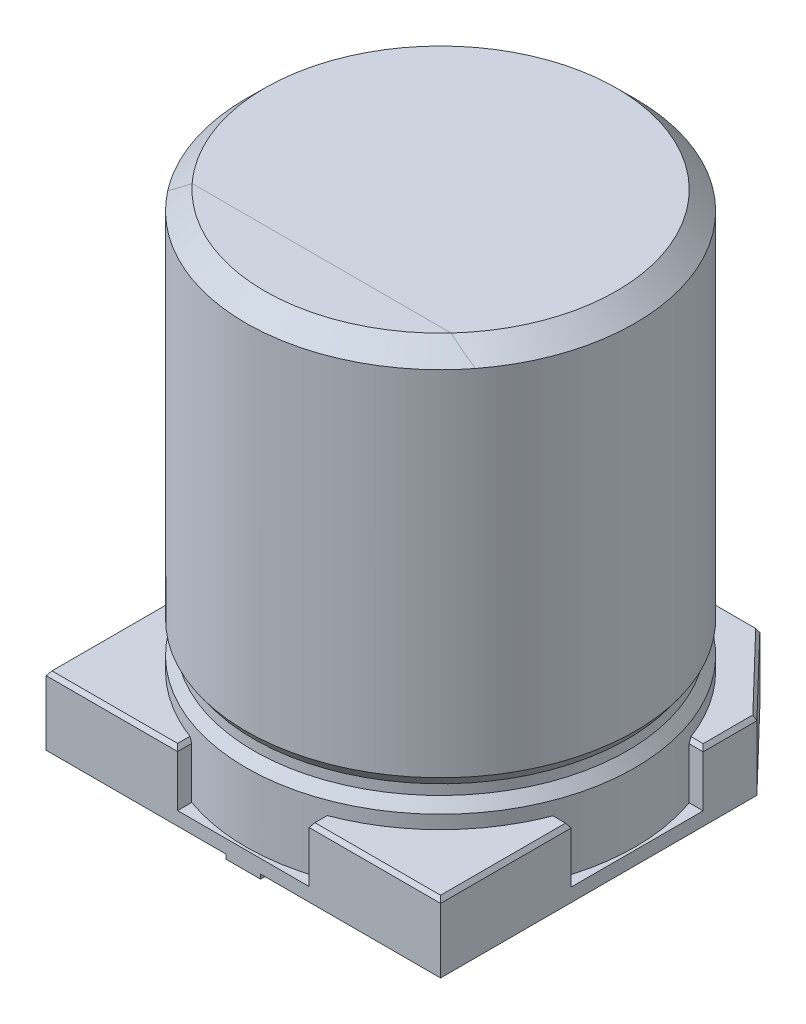
SolidWorks part; units mm, degrees
ref_plane "Front Plane" through (0, 0, 0) normal (0, 0, 1) x (1, 0, 0)
ref_plane "Top Plane" through (0, 0, 0) normal (0, 1, 0) x (1, 0, 0)
ref_plane "Right Plane" through (0, 0, 0) normal (1, 0, 0) x (0, 0, -1)
sketch "Sketch1" plane through (0, 0, 0) normal (0, 1, 0) x (1, 0, 0)
  line L0 (0, 3.315) -> (0, -3.315) construction
  point P2 (0, 0)
  line B0 (3.315, -3.315) -> (3.315, 2.0024)
  line B1 (0.2896, -3.315) -> (3.315, -3.315)
  line B2 (2.0517, 3.315) -> (3.315, 2.0024)
  line B3 (2.0517, 3.315) -> (0.2875, 3.315)
  line B4 (0.2882, 1.5924) -> (0.2875, 3.315)
  line B5 (0.2875, 3.315) -> (-0.2875, 3.315)
  line B6 (-0.2875, 3.315) -> (-0.2882, 1.5924)
  line B7 (-0.2875, 3.315) -> (-2.0519, 3.315)
  line B8 (-0.2882, 1.5924) -> (0.2882, 1.5924)
  line B9 (0.2889, -1.5924) -> (-0.2889, -1.5924)
  line B10 (0.2896, -3.315) -> (0.2889, -1.5924)
  line B11 (-0.2889, -1.5924) -> (-0.2896, -3.315)
  line B12 (-0.2896, -3.315) -> (0.2896, -3.315)
  line B13 (-3.315, -3.315) -> (-0.2896, -3.315)
  line B14 (-3.315, 2.0024) -> (-3.315, -3.315)
  line B15 (-3.315, 2.0024) -> (-2.0519, 3.315)
  line B16 (-3.315, -1.1187) -> (-1.11, -1.105)
  line B17 (-1.11, -1.105) -> (-1.105, -3.315)
  line B18 (-1.115, 1.105) -> (-3.315, 1.0983)
  line B19 (-1.12, 3.315) -> (-1.115, 1.105)
  line B20 (1.11, -1.105) -> (3.315, -1.1187)
  line B21 (1.105, -3.315) -> (1.11, -1.105)
  line B22 (1.115, 1.105) -> (1.12, 3.315)
  line B23 (3.315, 1.0983) -> (1.115, 1.105)
sketch_block_instance "Block1-1"
sketch_block "Block1"
extrude "Boss-Extrude1" add sketch "Sketch1" against normal blind 0.1571 contours B19 B7 B15 B14 B18 | L0 B8 B6 B7 B19 B18 B14 B16 B17 B13 B11 B9 | B17 B16 B14 B13 | B9 L0 B12 B10 | L0 B9 B11 B12 | L0 B5 B6 B8 | B5 L0 B8 B4 | B8 L0 B9 B10 B1 B21 B20 B0 B23 B22 B3 B4 | B23 B0 B2 B3 B22 | B21 B1 B0 B20 region at (0.1439, 0, -2.4533) region at (-0.1439, 0, -2.4533) region at (1.3107, 0, -0.0031) region at (-1.3107, 0, -0.0031) region at (0.1446, 0, 2.454) region at (-0.1446, 0, 2.454) region at (2.0777, 0, -2.0703) region at (-2.0777, 0, -2.0704) region at (-2.2101, 0, 2.2138) region at (2.2101, 0, 2.2138)
extrude "Boss-Extrude2" add sketch "Sketch1<4>" along normal blind 0.6443 contours B19 B7 B15 B14 B18 | B17 B16 B14 B13 | B23 B0 B2 B3 B22 | B21 B1 B0 B20 region at (2.2101, 0, 2.2138) region at (2.0777, 0, -2.0703) region at (-2.2101, 0, 2.2138) region at (-2.0777, 0, -2.0704)
sketch "Sketch1<4>" plane through (0, 0, 0) normal (0, 1, 0) x (1, 0, 0) same geometry as "Sketch1"
chamfer "Chamfer1" distance 0.0487 angle 45 18 edges at (2.2125, 0.6443, 1.1119) (3.315, 0.6443, 2.2169) (2.21, 0.6443, 3.315) (1.1075, 0.6443, 2.21) (1.1175, 0.6443, -2.21) (1.5858, 0.6443, -3.315) (2.6833, 0.6443, -2.6587) (3.315, 0.6443, -1.5504) (2.215, 0.6443, -1.1017) (-2.215, 0.6443, -1.1017) (-3.315, 0.6443, -1.5504) (-2.6835, 0.6443, -2.6587) (-1.586, 0.6443, -3.315) (-1.1175, 0.6443, -2.21) (-2.21, 0.6443, 3.315) (-3.315, 0.6443, 2.2169) (-2.2125, 0.6443, 1.1119) (-1.1075, 0.6443, 2.21)
extrude "Boss-Extrude3" add sketch "Sketch1<5>" against normal blind 0.0514 from surface contours L0 B9 B11 B12 | B9 L0 B12 B10 | L0 B5 B6 B8 | B5 L0 B8 B4 region at (0.1439, 0, -2.4533) region at (-0.1439, 0, -2.4533) region at (0.1446, 0, 2.454) region at (-0.1446, 0, 2.454) starting at face at (0, -0.1571, -0.6675)
sketch "Sketch1<5>" plane through (0, 0, 0) normal (0, 1, 0) x (1, 0, 0) same geometry as "Sketch1"
sketch "Sketch2" plane through (0, 0, 0) normal (0, 1, 0) x (1, 0, 0)
  circle A0 centre (0, 0) radius 3.27
  dimension "D1" = 6.54
extrude "Boss-Extrude4" add sketch "Sketch2" along normal blind 5.5
chamfer "Chamfer2" distance 0.2155 distance2 0.314 1 edges at (0, 5.5, 3.27) first distance on face at (0, 0.4133, 0.0057)
ref_axis "Axis1" through (0, 5.2845, 0) along (0, -1, 0)
sketch "Sketch3" plane through (0, 0, 0) normal (0, 0, 1) x (1, 0, 0)
  line L0 (3.1392, 1.0429) -> (3.1392, 0.9251)
  line L1 (3.27, 0) -> (3.27, 5.2845) construction
  line L2 (3.27, 1.168) -> (3.1392, 1.0429)
  line L3 (3.27, 1.168) -> (3.27, 0.8)
  line L4 (3.27, 0.984) -> (0, 0.984) construction
  line L5 (0, 5.2845) -> (0, 0) construction
  line L6 (3.27, 0.8) -> (3.1392, 0.9251)
  line L7 (1.1055, 0) -> (-1.1055, 0) construction
  point P10 (3.1392, 0.984)
  dimension "D1" = 0.368
  dimension "D2" = 0.1308
  dimension "D3" = 0.1251
  dimension "D4" = 0.8
revolve "Cut-Revolve1" cut sketch "Sketch3" angle 360 about axis through (0, 5.2845, 0) along (0, -1, 0)
sketch "Sketch4" plane through (0, 5.5, 0) normal (0, 1, 0) x (1, 0, 0)
  line L0 (-2.5871, -2) -> (2.5871, -2)
  arc A0 (-3.0551, -1.1658) -> (-1.1543, -3.0595) centre (0, 0) ccw construction
  arc A1 (1.1543, -3.0595) -> (3.0551, -1.1658) centre (0, 0) ccw construction
  dimension "D1" = 2
split line "Split Line1"
sketch "Sketch5" plane through (0, -0.1571, 0) normal (0, -1, 0) x (1, 0, 0)
  circle A0 centre (0, 0) radius 1 construction
  dimension "D1" = 2
scale "Scale1" scale about centroid uniform scaling no x scale factor 0.651376 y scale factor 0.939929 z scale factor 0.651376
